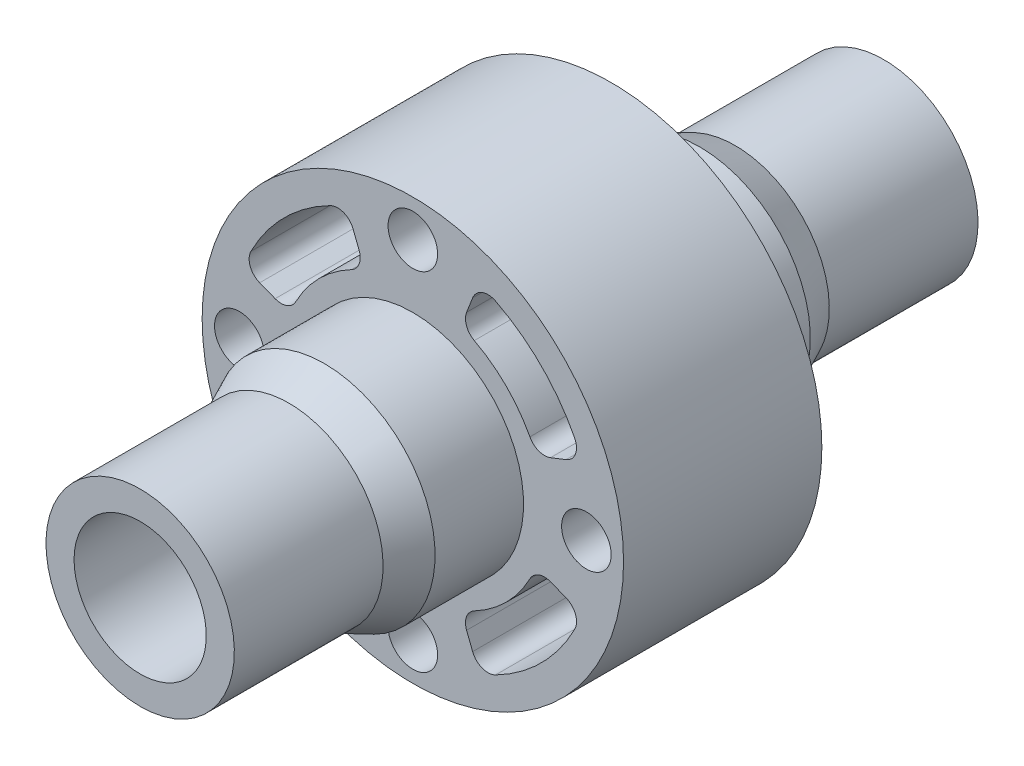
SolidWorks part; units mm, degrees
ref_plane "前视基准面" through (0, 0, 0) normal (0, 0, 1) x (1, 0, 0)
ref_plane "上视基准面" through (0, 0, 0) normal (0, 1, 0) x (1, 0, 0)
ref_plane "右视基准面" through (0, 0, 0) normal (1, 0, 0) x (0, 0, -1)
sketch "草图1" plane through (0, 0, 0) normal (1, 0, 0) x (0, 0, -1)
  line L0 (-21.2214, 0) -> (28.1258, 0) construction
  line L1 (-22.5, 0) -> (-22.5, 5.7)
  line L2 (-22.5, 5.7) -> (-13.5, 5.7)
  line L3 (-13.5, 5.7) -> (-13.5, 6.7) construction
  line L4 (-11.3555, 6.7) -> (-6, 6.7)
  line L5 (-6, 6.7) -> (-6, 14)
  line L6 (-6, 14) -> (6, 14)
  line L7 (0, 14) -> (0, 0) construction
  line L8 (6, 6.7) -> (6, 14)
  line L9 (11.3555, 6.7) -> (6, 6.7)
  line L10 (13.5, 5.7) -> (13.5, 6.7) construction
  line L11 (22.5, 5.7) -> (13.5, 5.7)
  line L12 (22.5, 0) -> (22.5, 5.7)
  line L13 (-22.5, 0) -> (22.5, 0)
  line L14 (-13.5, 5.7) -> (-11.3555, 6.7)
  line L15 (-13.5, 6.7) -> (-11.3555, 6.7) construction
  line L16 (13.5, 5.7) -> (11.3555, 6.7)
  line L17 (13.5, 6.7) -> (11.3555, 6.7) construction
  dimension "D1" = 5.7
  dimension "D2" = 12
  dimension "D3" = 14
  dimension "D4" = 9
  dimension "D5" = 7.5
  dimension "D6" = 6.7
  dimension "D7" = 45
  dimension "D8" = 25
revolve "旋转1" add sketch "草图1" angle 360 about L13
sketch "草图2" plane through (0, 0, 6) normal (0, 0, 1) x (1, 0, 0)
  line L0 (0, 0) -> (0, 10.5) construction
  circle A0 centre (0, 0) radius 10.5 construction
  circle A1 centre (0, 10.5) radius 1.5
  circle A2 centre (0, 0) radius 10.5 construction
  circle A3 centre (10.5, 0) radius 1.5
  circle A4 centre (0, 0) radius 10.5 construction
  circle A5 centre (0, -10.5) radius 1.5
  circle A6 centre (0, 0) radius 10.5 construction
  circle A7 centre (-10.5, 0) radius 1.5
  dimension "D1" = 21
  dimension "D2" = 3
  dimension "D3" = 4
extrude "切除-拉伸1" cut sketch "草图2" against normal through all
sketch "草图4" plane through (0, 0, -6) normal (0, 0, -1) x (-1, 0, 0)
  circle A0 centre (0, 0) radius 12.75
  circle A1 centre (0, 0) radius 14 construction
  circle A2 centre (0, 0) radius 14
  dimension "D1" = 25.5
extrude "切除-拉伸4" cut sketch "草图4" against normal through all
sketch "草图5" plane through (0, 0, -6) normal (0, 0, -1) x (-1, 0, 0)
  line L0 (-9.2687, 3.6181) -> (-8.332, 3.2525)
  line L1 (-3.6181, 9.2687) -> (-3.2525, 8.332)
  line L8 (3.6181, 9.2687) -> (3.2525, 8.332)
  line L9 (9.2687, 3.6181) -> (8.332, 3.2525)
  line L10 (9.2687, -3.6181) -> (8.332, -3.2525)
  line L11 (3.6181, -9.2687) -> (3.2525, -8.332)
  line L12 (-3.6181, -9.2687) -> (-3.2525, -8.332)
  line L13 (-9.2687, -3.6181) -> (-8.332, -3.2525)
  circle A2 centre (-10.5, 0) radius 1.5 construction
  circle A4 centre (0, 10.5) radius 1.5 construction
  arc A6 (-3.7191, 7.083) -> (-7.083, 3.7191) centre (0, 0) ccw
  arc A7 (-5.0046, 9.7956) -> (-9.7956, 5.0046) centre (0, 0) ccw
  arc A14 (-8.332, 3.2525) -> (-7.083, 3.7191) centre (-7.9683, 4.184) ccw
  arc A15 (-9.2687, 3.6181) -> (-9.7956, 5.0046) centre (-8.9051, 4.5497) cw
  arc A16 (-3.2525, 8.332) -> (-3.7191, 7.083) centre (-4.184, 7.9683) cw
  arc A17 (-3.6181, 9.2687) -> (-5.0046, 9.7956) centre (-4.5497, 8.9051) ccw
  arc A18 (3.6181, 9.2687) -> (5.0046, 9.7956) centre (4.5497, 8.9051) cw
  arc A19 (3.2525, 8.332) -> (3.7191, 7.083) centre (4.184, 7.9683) ccw
  arc A20 (7.083, 3.7191) -> (3.7191, 7.083) centre (0, 0) ccw
  arc A21 (8.332, 3.2525) -> (7.083, 3.7191) centre (7.9683, 4.184) cw
  arc A22 (9.2687, 3.6181) -> (9.7956, 5.0046) centre (8.9051, 4.5497) ccw
  arc A23 (9.7956, 5.0046) -> (5.0046, 9.7956) centre (0, 0) ccw
  arc A24 (9.2687, -3.6181) -> (9.7956, -5.0046) centre (8.9051, -4.5497) cw
  arc A25 (8.332, -3.2525) -> (7.083, -3.7191) centre (7.9683, -4.184) ccw
  arc A26 (3.7191, -7.083) -> (7.083, -3.7191) centre (0, 0) ccw
  arc A27 (3.2525, -8.332) -> (3.7191, -7.083) centre (4.184, -7.9683) cw
  arc A28 (3.6181, -9.2687) -> (5.0046, -9.7956) centre (4.5497, -8.9051) ccw
  arc A29 (5.0046, -9.7956) -> (9.7956, -5.0046) centre (0, 0) ccw
  arc A30 (-3.6181, -9.2687) -> (-5.0046, -9.7956) centre (-4.5497, -8.9051) cw
  arc A31 (-3.2525, -8.332) -> (-3.7191, -7.083) centre (-4.184, -7.9683) ccw
  arc A32 (-7.083, -3.7191) -> (-3.7191, -7.083) centre (0, 0) ccw
  arc A33 (-8.332, -3.2525) -> (-7.083, -3.7191) centre (-7.9683, -4.184) cw
  arc A34 (-9.2687, -3.6181) -> (-9.7956, -5.0046) centre (-8.9051, -4.5497) ccw
  arc A35 (-9.7956, -5.0046) -> (-5.0046, -9.7956) centre (0, 0) ccw
  point P23 (0, 0)
  point P25 (0, 0)
  point P27 (-10.247, 4)
  point P32 (-4, 10.247)
  point P44 (0, 0)
  point P57 (0, 0)
  point P63 (0, 0)
  dimension "D3" = 11
  dimension "D4" = 8
  dimension "D6" = 1
  dimension "D1" = 4
  dimension "D2" = 4
extrude "切除-拉伸5" cut sketch "草图5" against normal through all
sketch "草图6" plane through (0, 0, -22.5) normal (0, 0, -1) x (-1, 0, 0)
  circle A0 centre (0, 0) radius 4
  dimension "D1" = 8
extrude "切除-拉伸6" cut sketch "草图6" against normal through all
move or copy body "实体-移动/复制1" [suppressed] bodies to move or copy 113
